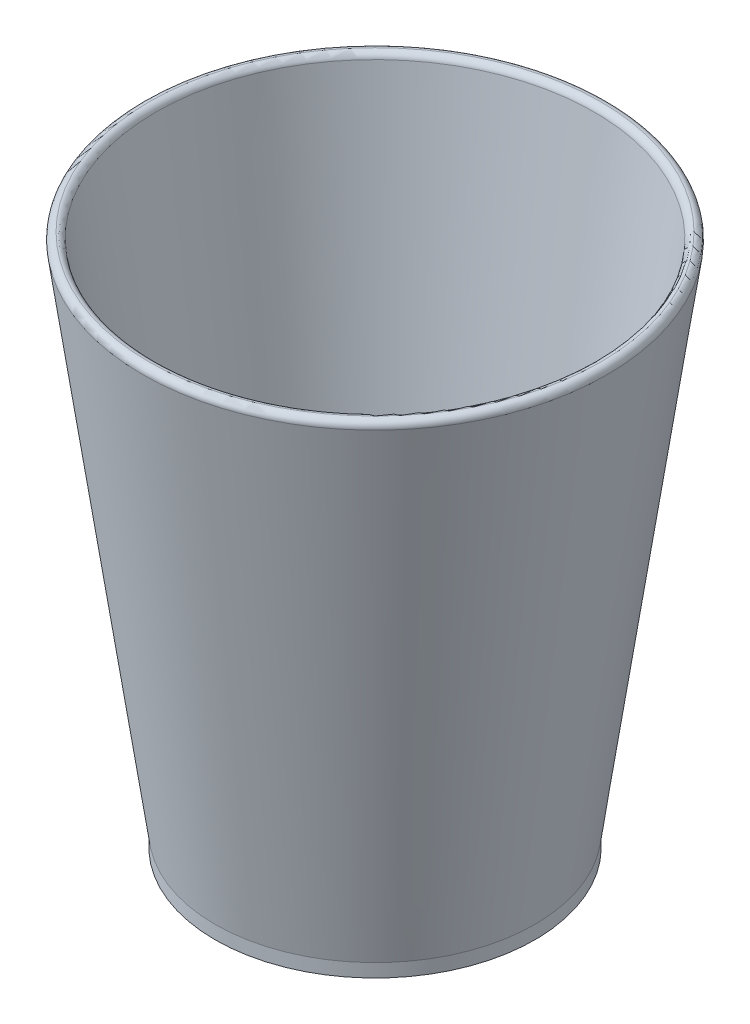
SolidWorks part; units mm, degrees
ref_plane "Alzado" through (0, 0, 0) normal (0, 0, 1) x (1, 0, 0)
ref_plane "Planta" through (0, 0, 0) normal (0, 1, 0) x (1, 0, 0)
ref_plane "Vista lateral" through (0, 0, 0) normal (1, 0, 0) x (0, 0, -1)
sketch "Croquis1" plane through (0, 0, 0) normal (0, 1, 0) x (1, 0, 0)
  circle A0 centre (0, 0) radius 24
  dimension "D1" = 48
extrude "Saliente-Extruir1" add sketch "Croquis1" along normal blind 2
sketch "Croquis2" plane through (0, 0, 0) normal (0, 0, 1) x (1, 0, 0)
  line L0 (0, 2) -> (0, 80) construction
  line L1 (24, 2) -> (-24, 2) construction
  line L2 (0, 80) -> (35, 80) construction
  line L3 (24, 2) -> (35, 80)
  line L4 (35, 80) -> (33, 80)
  line L5 (33, 80) -> (22, 2)
  line L6 (22, 2) -> (24, 2)
revolve "Revolución1" add sketch "Croquis2" angle 360 about L0
fillet "Redondeo1" radius 1 1 edges at (35, 80, 0)
fillet "Redondeo2" radius 1 1 edges at (33, 80, 0)
